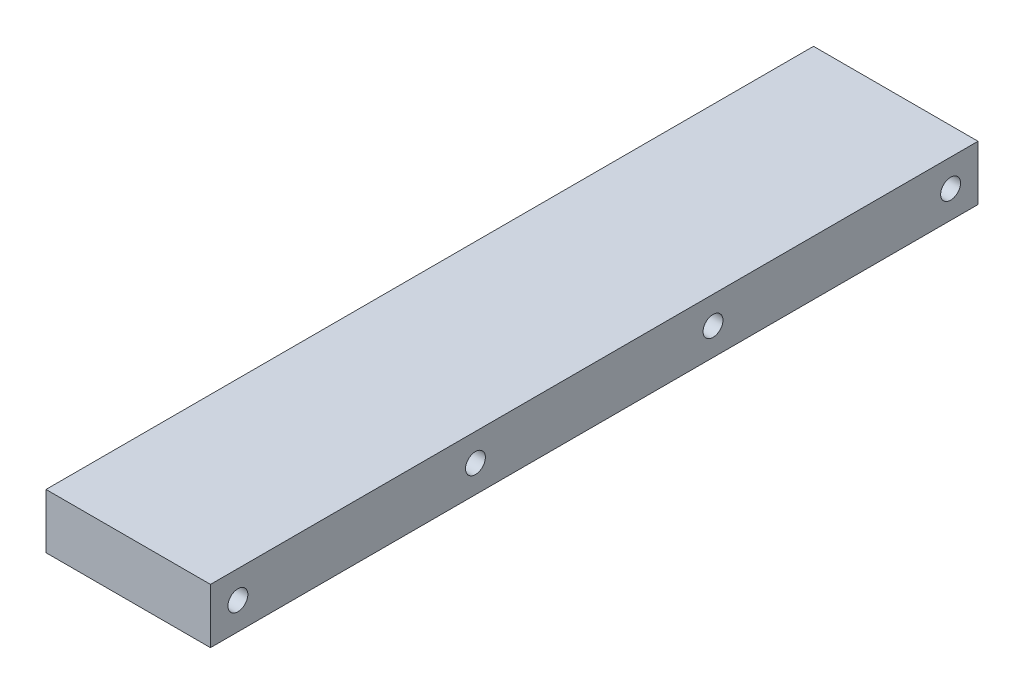
SolidWorks part; units mm, degrees
ref_plane "Front Plane" through (0, 0, 0) normal (0, 0, 1) x (1, 0, 0)
ref_plane "Top Plane" through (0, 0, 0) normal (0, 1, 0) x (1, 0, 0)
ref_plane "Right Plane" through (0, 0, 0) normal (1, 0, 0) x (0, 0, -1)
sketch "Sketch2" plane through (0, 0, 0) normal (0, 1, 0) x (1, 0, 0)
  line L0 (0, 0) -> (28.575, 0)
  line L1 (28.575, 0) -> (28.575, 133.35)
  line L2 (28.575, 133.35) -> (0, 133.35)
  line L3 (0, 133.35) -> (0, 0)
  dimension "D1" = 133.35
  dimension "D2" = 28.575
extrude "Boss-Extrude1" add sketch "Sketch2" along normal blind 9.525
sketch "Sketch3" plane through (28.575, 0, 0) normal (1, 0, 0) x (0, 0, -1)
  line L0 (0, 9.525) -> (0, 0) construction
  line L1 (0, 9.525) -> (133.35, 9.525) construction
  point P0 (4.7625, 4.7625)
  dimension "D1" = 4.7625
  dimension "D2" = 4.7625
sketch "Sketch4" plane through (28.575, 0, 0) normal (1, 0, 0) x (0, 0, -1)
  point P0 (4.7625, 4.7625)
hole_wizard "#5 Clearance Hole1" positions "Sketch4" profile "Sketch5" hole size "#5" standard "ANSI Inch"
sketch "Sketch5" plane through (28.575, 4.7625, -4.7625) normal (0, 1, 0) x (0, 0, -1)
  line L0 (0, 0) -> (0, 13.7378)
  line L1 (0, 13.7378) -> (1.7272, 12.7)
  line L2 (1.7272, 12.7) -> (1.7272, 0)
  line L5 (1.7272, 0) -> (0, 0)
  line L10 (0, 13.7378) -> (-1.7272, 12.7) construction
  line L11 (0, -6.35) -> (0, 107.95) construction
  dimension "Hole Dia." = 3.4544
  dimension "Hole Depth" = 12.7
  dimension "Drill Angle" = 118
pattern_linear "LPattern1" count 4 spacing 41.275 along (0, 0, -1) of "#5 Clearance Hole1"
sketch "Sketch6" plane through (0, 0, 0) normal (-1, 0, 0) x (0, 0, 1)
  line L0 (-133.35, 9.525) -> (-133.35, 0) construction
  line L1 (-133.35, 9.525) -> (0, 9.525) construction
  point P0 (-128.5875, 4.7625)
  dimension "D1" = 4.7625
  dimension "D2" = 4.7625
hole_wizard "#5 Clearance Hole2" positions "Sketch6" profile "Sketch7" hole size "#5" standard "ANSI Inch"
sketch "Sketch7" plane through (0, 4.7625, -128.5875) normal (0, 1, 0) x (0, 0, 1)
  line L0 (0, 0) -> (0, 13.7378)
  line L1 (0, 13.7378) -> (1.7272, 12.7)
  line L2 (1.7272, 12.7) -> (1.7272, 0)
  line L5 (1.7272, 0) -> (0, 0)
  line L10 (0, 13.7378) -> (-1.7272, 12.7) construction
  line L11 (0, -6.35) -> (0, 107.95) construction
  dimension "Hole Dia." = 3.4544
  dimension "Hole Depth" = 12.7
  dimension "Drill Angle" = 118
pattern_linear "LPattern2" count 4 spacing 41.275 along (0, 0, 1) of "#5 Clearance Hole2"
